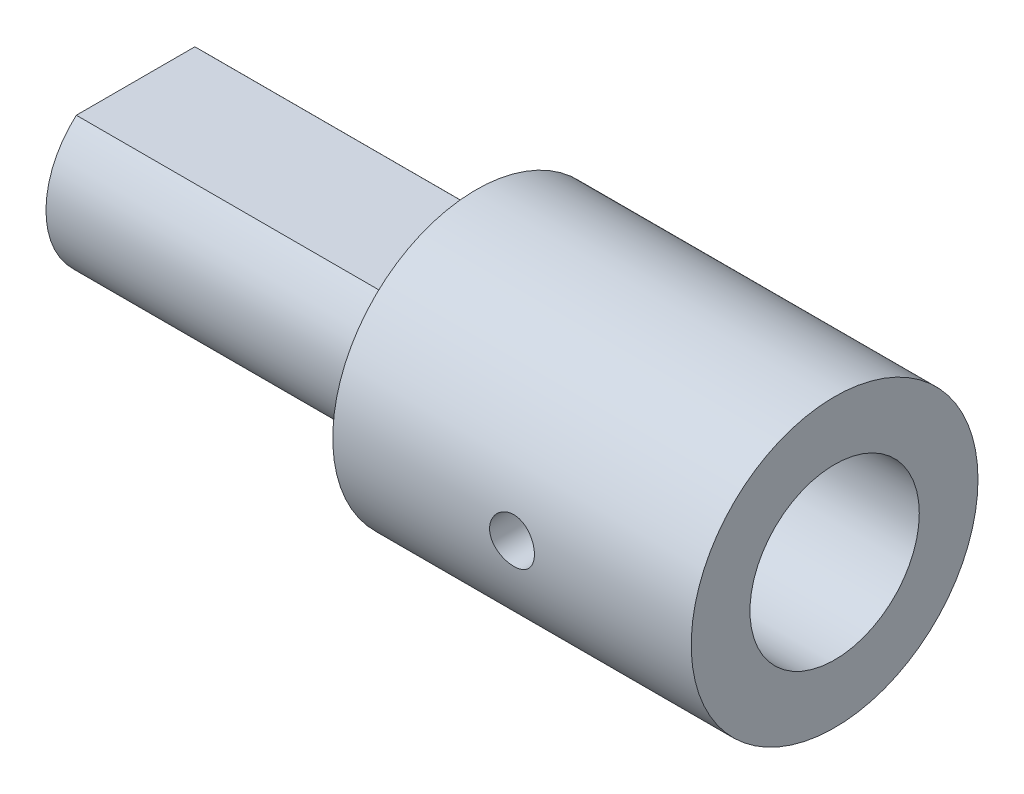
SolidWorks part; units mm, degrees
ref_plane "Front Plane" through (0, 0, 0) normal (1, 0, 0) x (0, 1, 0)
ref_plane "Top Plane" through (0, 0, 0) normal (0, 0, 1) x (0, 1, 0)
ref_plane "Right Plane" through (0, 0, 0) normal (0, 1, 0) x (-1, 0, 0)
sketch "Sketch1" plane through (0, 0, 0) normal (1, 0, 0) x (0, 1, 0)
  circle A0 centre (0, 0) radius 5.08
  point P3 (0, 0)
  dimension "D1" = 10.16
extrude "Boss-Extrude1" add sketch "Sketch1" along normal blind 12.7
sketch "Sketch2" plane through (12.7, 0, 0) normal (1, 0, 0) x (0, 1, 0)
  circle A0 centre (0, 0) radius 3
  dimension "D1" = 6
extrude "Cut-Extrude1" cut sketch "Sketch2" against normal blind 9.5413
sketch "Sketch3" plane through (0, 0, 0) normal (-1, 0, 0) x (0, -1, 0)
  circle A0 centre (0, 0) radius 3.175
  dimension "D1" = 6.35
extrude "Boss-Extrude2" add sketch "Sketch3" along normal blind 12.065
sketch "Sketch4" plane through (0, 0, 0) normal (0, 0, 1) x (0, 1, 0)
  line L0 (0, -12.7) -> (0, -6.35) construction
  line L1 (-5.08, -12.7) -> (5.08, -12.7) construction
  circle A0 centre (0, -6.35) radius 0.7938
  point P1 (0, -6.35)
  dimension "D2" = 1.5875
  dimension "D1" = 6.35
extrude "Cut-Extrude2" cut sketch "Sketch4" against normal blind 7.62 and the other way blind 7.62 contours A0
sketch "Sketch7" plane through (-12.065, 0, 0) normal (-1, 0, 0) x (0, -1, 0)
  line L1 (-2.3812, 2.1001) -> (-3.175, 2.1001)
  line L2 (-2.3812, 2.1001) -> (-2.3812, -2.1001)
  line L3 (-2.3812, -2.1001) -> (-3.175, -2.1001)
  line L4 (-3.175, 2.1001) -> (-3.175, -2.1001)
  circle A0 centre (0, 0) radius 3.175 construction
  circle A1 centre (0, 0) radius 3.175 construction
  point P6 (0, 0)
  point P9 (-3.175, 0)
  dimension "D1" = 0.7937
extrude "Cut-Extrude3" cut sketch "Sketch7" against normal blind 12.065
